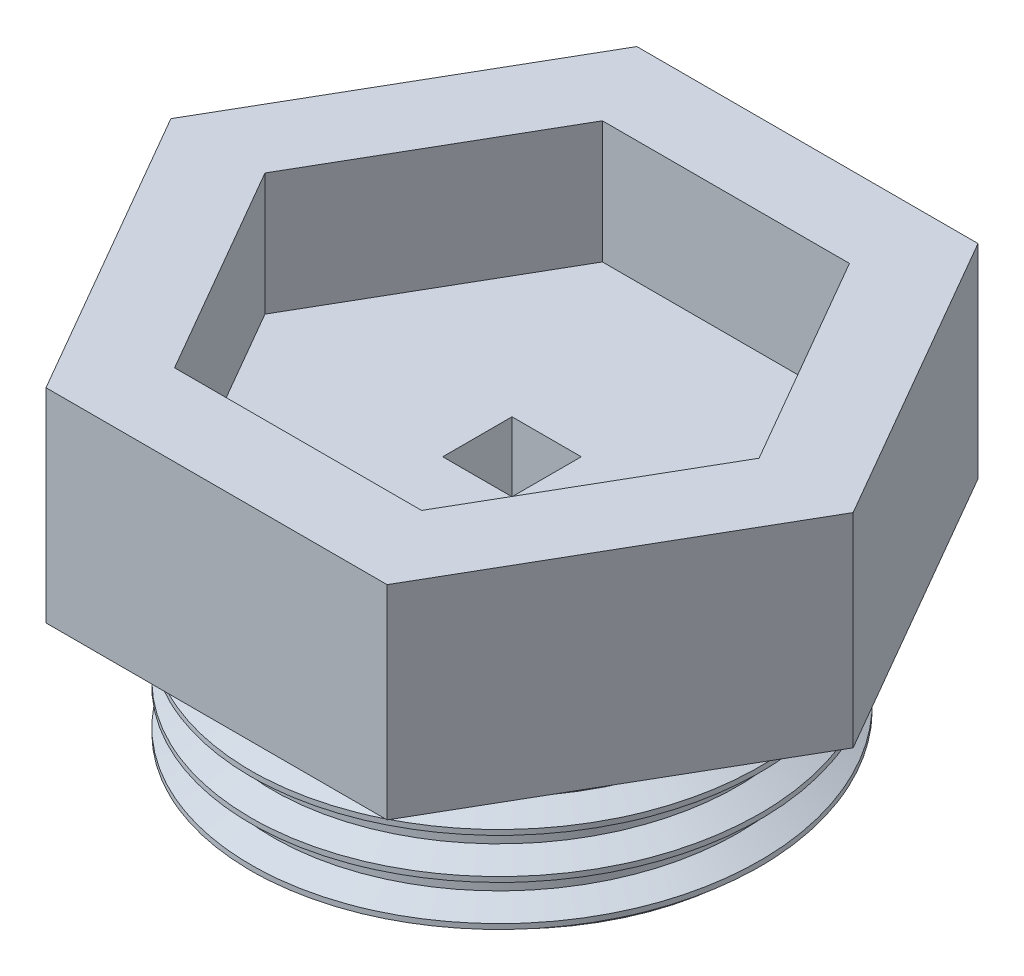
SolidWorks part; units mm, degrees
ref_plane "Front Plane" through (0, 0, 0) normal (0, 0, 1) x (1, 0, 0)
ref_plane "Top Plane" through (0, 0, 0) normal (0, 1, 0) x (1, 0, 0)
ref_plane "Right Plane" through (0, 0, 0) normal (1, 0, 0) x (0, 0, -1)
sketch "Sketch1" plane through (0, 0, 0) normal (0, 1, 0) x (1, 0, 0)
  circle A0 centre (0, 0) radius 6.25
  dimension "D1" = 12.5
extrude "Boss-Extrude1" add sketch "Sketch1" along normal blind 4
thread "Thread1" pitch 1 method cut profile "Thread Profile1" start angle 0, offset 0, length 0, pitch 1, diameter 12.5
ref_plane "Plane1" through (-6.25, 4, 0) normal (0, 0, 1) x (-1, 0, 0)
sketch "Thread Profile1" plane through (-6.25, 4, 0) normal (0, 0, 1) x (-1, 0, 0)
  line L0 (0, 0) -> (0, 1) construction
  line L11 (0, 0) -> (0, 0.875)
  line L12 (0, 0.875) -> (-0.5413, 0.5625)
  line L13 (-0.5413, 0.5625) -> (-0.5413, 0.3125)
  line L15 (-0.5413, 0.3125) -> (0, 0)
  line L17 (-0.5413, 0.4375) -> (0, 0.4375) construction
  point P2 (0, 0)
  dimension "Pitch" = 1
  dimension "Profile_Angle" = 60
  dimension "Profile_Land" = 0.25
  dimension "Profile_Height" = 0.5413
sketch "Sketch4" plane through (0, 4, 0) normal (0, 1, 0) x (1, 0, 0)
  line L1 (8.3716, 0) -> (4.1858, 7.25)
  line L2 (4.1858, 7.25) -> (-4.1858, 7.25)
  line L3 (-4.1858, 7.25) -> (-8.3716, 0)
  line L4 (-8.3716, 0) -> (-4.1858, -7.25)
  line L5 (-4.1858, -7.25) -> (4.1858, -7.25)
  line L6 (4.1858, -7.25) -> (8.3716, 0)
  circle A2 centre (0, 0) radius 7.25 construction
  circle A3 centre (0, 0) radius 6.25 construction
  dimension "D1" = 1
extrude "Boss-Extrude2" add sketch "Sketch4" along normal blind 5
sketch "Sketch5" plane through (0, 9, 0) normal (0, 1, 0) x (1, 0, 0)
  line L0 (8.3716, 0) -> (4.1858, 7.25) construction
  line L1 (3.0311, 5.25) -> (-3.0311, 5.25)
  line L2 (-3.0311, 5.25) -> (-6.0622, 0)
  line L3 (-6.0622, 0) -> (-3.0311, -5.25)
  line L4 (-3.0311, -5.25) -> (3.0311, -5.25)
  line L5 (3.0311, -5.25) -> (6.0622, 0)
  line L6 (6.0622, 0) -> (3.0311, 5.25)
  circle A0 centre (0, 0) radius 5.25 construction
  dimension "D1" = 2
extrude "Cut-Extrude1" cut sketch "Sketch5" against normal offset from surface (3 mm away) 2 up to face at (0, 4, 0)
sketch "Sketch6" plane through (0, 6, 0) normal (0, 1, 0) x (1, 0, 0)
  line L1 (-0.85, -0.85) -> (0.85, -0.85)
  line L2 (-0.85, -0.85) -> (-0.85, 0.85)
  line L3 (-0.85, 0.85) -> (0.85, 0.85)
  line L4 (0.85, -0.85) -> (0.85, 0.85)
  line L5 (-0.85, -0.85) -> (0.85, 0.85) construction
  line L6 (-0.85, 0.85) -> (0.85, -0.85) construction
  point P0 (0, 0)
  dimension "D1" = 1.7
  dimension "D2" = 1.7
extrude "Cut-Extrude2" cut sketch "Sketch6" against normal through all both and the other way through all
equation "\"diameter_electrode_outer\"= 13mm"
equation "\"height_thread\"= 4mm"
equation "\"D1@Sketch1\"=\"diameter_electrode_outer\"-\"offset\""
equation "\"D1@Boss-Extrude1\"=\"height_thread\""
equation "\"diameter_tube\"= 2mm"
equation "\"offset\"= 0.5mm"
equation "\"height_turning_knob\"= 5mm"
equation "\"D1@Boss-Extrude2\"=\"height_turning_knob\""
equation "\"D1@Sketch5\"=2mm"
equation "\"width_dupont\"= 1.7mm"
equation "\"height_dupont\"= 1.7mm"
equation "\"length_dupont\"= 11.5mm"
equation "\"D1@Sketch6\"=\"width_dupont\""
equation "\"D2@Sketch6\"=\"width_dupont\""
